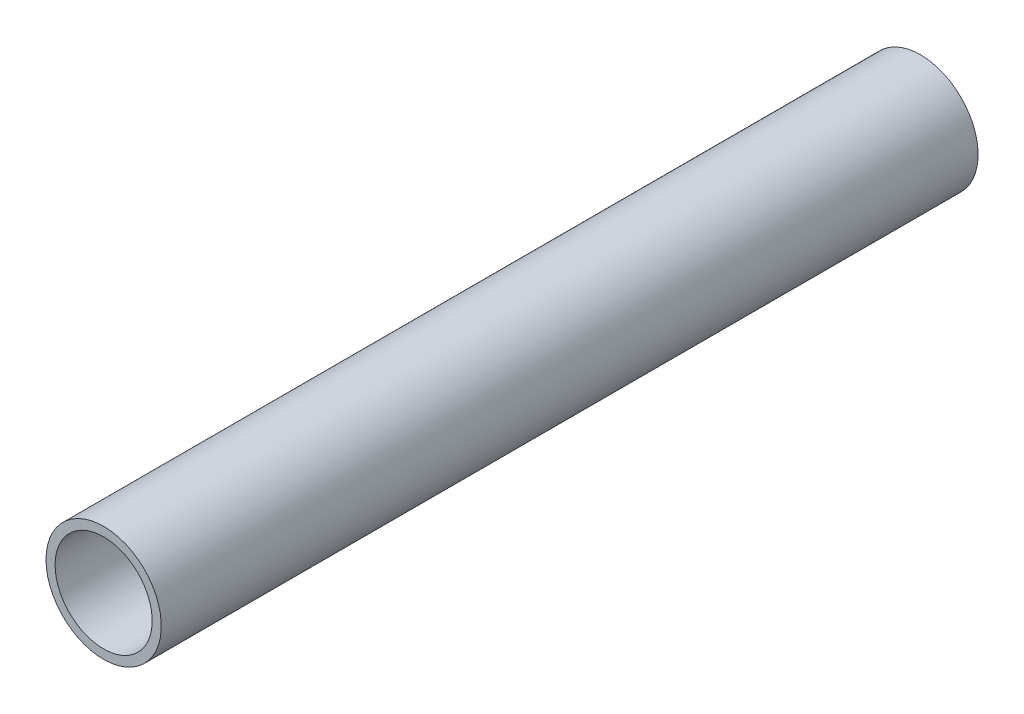
SolidWorks part; units mm, degrees
material "Hexcel AS4C (3000 Filaments)"
ref_plane "Front Plane" through (0, 0, 0) normal (0, 0, 1) x (1, 0, 0)
ref_plane "Top Plane" through (0, 0, 0) normal (0, 1, 0) x (1, 0, 0)
ref_plane "Right Plane" through (0, 0, 0) normal (1, 0, 0) x (0, 0, -1)
sketch "Sketch1" plane through (0, 0, 0) normal (0, 0, 1) x (1, 0, 0)
  circle A0 centre (0, 0) radius 12.7
  circle A1 centre (0, 0) radius 10.7
  dimension "D1" = 25.4
  dimension "D2" = 2
extrude "Boss-Extrude1" add sketch "Sketch1" along normal blind 180
